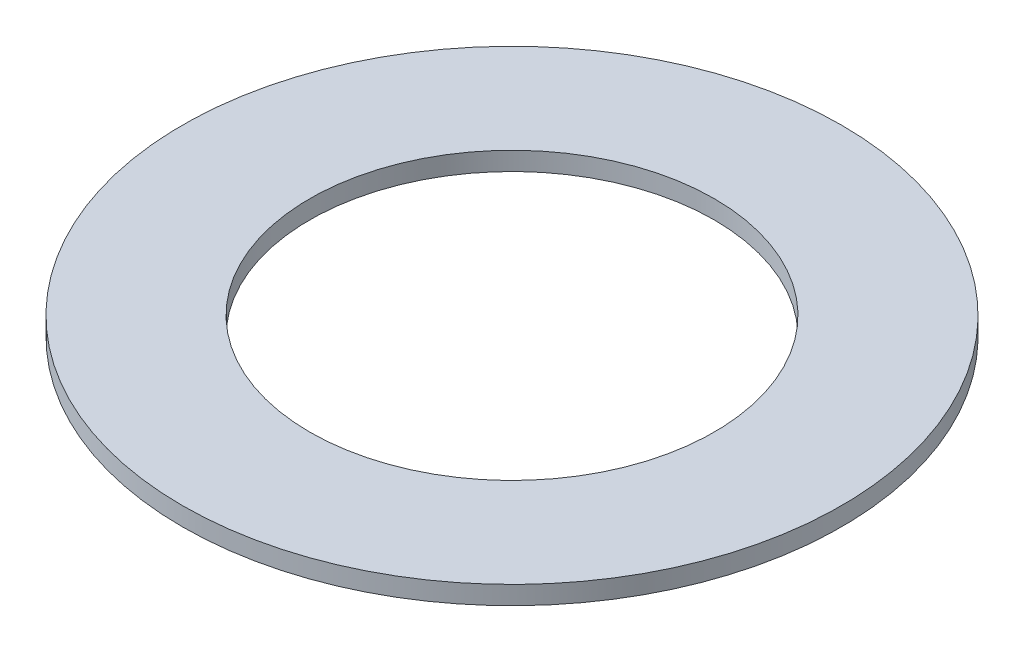
SolidWorks part; units mm, degrees
ref_plane "Front Plane" through (0, 0, 0) normal (0, 0, 1) x (1, 0, 0)
ref_plane "Top Plane" through (0, 0, 0) normal (0, 1, 0) x (1, 0, 0)
ref_plane "Right Plane" through (0, 0, 0) normal (1, 0, 0) x (0, 0, -1)
sketch "Sketch1" plane through (0, 0, 0) normal (0, 1, 0) x (1, 0, 0)
  circle A0 centre (0, 0) radius 3.429
  circle A1 centre (0, 0) radius 5.588
  dimension "D1" = 11.176
  dimension "D2" = 6.858
extrude "Boss-Extrude1" add sketch "Sketch1" along normal blind 0.3125
